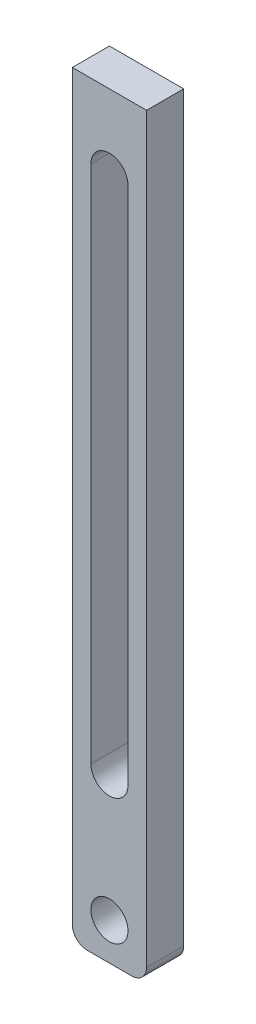
SolidWorks part; units mm, degrees
ref_plane "Front Plane" through (0, 0, 0) normal (0, 0, 1) x (1, 0, 0)
ref_plane "Top Plane" through (0, 0, 0) normal (0, 1, 0) x (1, 0, 0)
ref_plane "Right Plane" through (0, 0, 0) normal (1, 0, 0) x (0, 0, -1)
sketch "Sketch1" plane through (0, 0, 0) normal (0, 0, 1) x (1, 0, 0)
  line L1 (-3.81, -64.77) -> (3.81, -64.77)
  line L2 (-6.35, -62.23) -> (-6.35, 64.77)
  line L3 (-6.35, 64.77) -> (6.35, 64.77)
  line L4 (6.35, -62.23) -> (6.35, 64.77)
  line L5 (-6.35, -64.77) -> (6.35, 64.77) construction
  line L6 (-6.35, 64.77) -> (6.35, -64.77) construction
  circle A0 centre (0, -58.42) radius 3.175
  arc A1 (3.81, -64.77) -> (6.35, -62.23) centre (3.81, -62.23) ccw
  arc A2 (-3.81, -64.77) -> (-6.35, -62.23) centre (-3.81, -62.23) cw
  point P0 (0, 0)
  dimension "D1" = 6.35
  dimension "D3" = 2.54
  dimension "D2" = 12.7
  dimension "D4" = 6.35
  dimension "D5" = 127
extrude "Boss-Extrude1" add sketch "Sketch1" along normal blind 6.35
sketch "Sketch2" plane through (0, 0, 6.35) normal (0, 0, 1) x (1, 0, 0)
  line L4 (0, -36.83) -> (0, 52.07) construction
  line L5 (-3.175, -36.83) -> (-3.175, 52.07)
  line L6 (3.175, -36.83) -> (3.175, 52.07)
  line L7 (6.35, 64.77) -> (-6.35, 64.77) construction
  arc A2 (-3.175, -36.83) -> (3.175, -36.83) centre (0, -36.83) ccw
  arc A3 (3.175, 52.07) -> (-3.175, 52.07) centre (0, 52.07) ccw
  point P12 (0, 7.62)
  dimension "D4" = 6.35
  dimension "D5" = 12.7
  dimension "D6" = 101.6
extrude "Cut-Extrude1" cut sketch "Sketch2" against normal through all both
